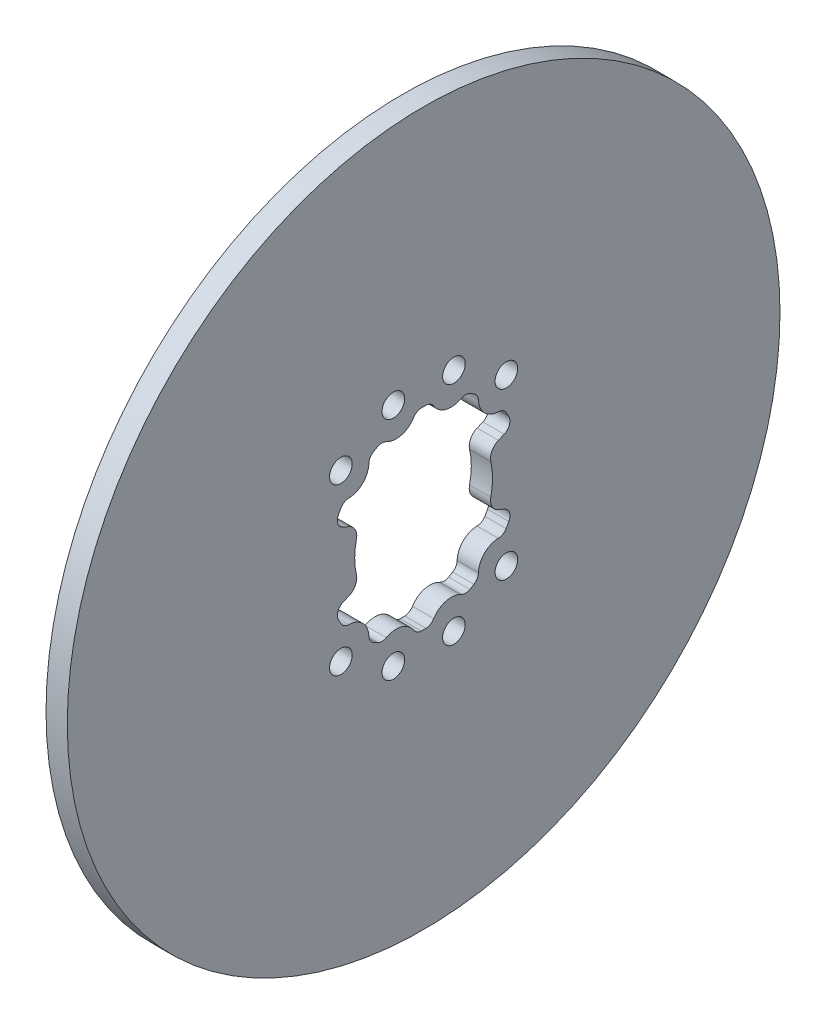
SolidWorks part; units mm, degrees
material "AR500"
ref_plane "Front Plane" through (0, 0, 0) normal (0, 0, 1) x (1, 0, 0)
ref_plane "Top Plane" through (0, 0, 0) normal (0, 1, 0) x (1, 0, 0)
ref_plane "Right Plane" through (0, 0, 0) normal (1, 0, 0) x (0, 0, -1)
sketch "Sketch1" plane through (0, 0, 0) normal (1, 0, 0) x (0, 0, -1)
  circle A0 centre (0, 0) radius 106.3625
  dimension "D1" = 212.725
extrude "Boss-Extrude1" add sketch "Sketch1" along normal blind 6.35
sketch "Sketch2" plane through (6.35, 0, 0) normal (1, 0, 0) x (0, 0, -1)
  line L0 (-9.0393, 33.735) -> (9.0393, 33.735) construction
  line B0 (22.31, -8.9662) -> (24.0357, -9.681)
  line B1 (-24.0357, -9.681) -> (-22.31, -8.9662)
  line B2 (-22.31, 8.9662) -> (-24.0357, 9.681)
  line B3 (24.0357, 9.681) -> (22.31, 8.9662)
  circle B4 centre (24.6957, -24.6957) radius 3.3782
  circle B5 centre (9.0393, -33.735) radius 3.3782
  circle B6 centre (-9.0393, -33.735) radius 3.3782
  circle B7 centre (-24.6957, -24.6957) radius 3.3782
  circle B8 centre (-24.6957, 24.6957) radius 3.3782
  circle B9 centre (-9.0393, 33.735) radius 3.3782
  circle B10 centre (9.0393, 33.735) radius 3.3782
  circle B11 centre (24.6957, 24.6957) radius 3.3782
  arc B12 (20.0543, -4.5952) -> (22.31, -8.9662) centre (23.768, -5.4462) ccw
  arc B13 (25.4311, -13.5782) -> (24.0357, -9.681) centre (22.9664, -12.2623) ccw
  arc B14 (24.6076, -15.0192) -> (25.4311, -13.5782) centre (0, 0) ccw
  arc B15 (22.2944, -16.3566) -> (24.6076, -15.0192) centre (22.2228, -13.5636) ccw
  arc B16 (22.2944, -16.3566) -> (16.3566, -22.2944) centre (22.4506, -22.4506) ccw
  arc B17 (15.0192, -24.6076) -> (16.3566, -22.2944) centre (13.5636, -22.2228) ccw
  arc B18 (13.8013, -25.3108) -> (15.0192, -24.6076) centre (0, 0) ccw
  arc B19 (11.1292, -25.3125) -> (13.8013, -25.3108) centre (12.4637, -22.8578) ccw
  arc B20 (11.1292, -25.3125) -> (3.0181, -27.4858) centre (8.2175, -30.6681) ccw
  arc B21 (0.7032, -28.8204) -> (3.0181, -27.4858) centre (0.635, -26.0273) ccw
  arc B22 (-0.7032, -28.8204) -> (0.7032, -28.8204) centre (0, 0) ccw
  arc B23 (-3.0181, -27.4858) -> (-0.7032, -28.8204) centre (-0.635, -26.0273) ccw
  arc B24 (-3.0181, -27.4858) -> (-11.1292, -25.3125) centre (-8.2175, -30.6681) ccw
  arc B25 (-13.8013, -25.3108) -> (-11.1292, -25.3125) centre (-12.4637, -22.8578) ccw
  arc B26 (-15.0192, -24.6076) -> (-13.8013, -25.3108) centre (0, 0) ccw
  arc B27 (-16.3566, -22.2944) -> (-15.0192, -24.6076) centre (-13.5636, -22.2228) ccw
  arc B28 (-16.3566, -22.2944) -> (-22.2944, -16.3566) centre (-22.4506, -22.4506) ccw
  arc B29 (-24.6076, -15.0192) -> (-22.2944, -16.3566) centre (-22.2228, -13.5636) ccw
  arc B30 (-25.4311, -13.5782) -> (-24.6076, -15.0192) centre (0, 0) ccw
  arc B31 (-24.0357, -9.681) -> (-25.4311, -13.5782) centre (-22.9664, -12.2623) ccw
  arc B32 (-22.31, -8.9662) -> (-20.0543, -4.5952) centre (-23.768, -5.4462) ccw
  arc B33 (-20.0543, 4.5952) -> (-20.0543, -4.5952) centre (0, 0) ccw
  arc B34 (-20.0543, 4.5952) -> (-22.31, 8.9662) centre (-23.768, 5.4462) ccw
  arc B35 (-25.4311, 13.5782) -> (-24.0357, 9.681) centre (-22.9664, 12.2623) ccw
  arc B36 (-24.6076, 15.0192) -> (-25.4311, 13.5782) centre (0, 0) ccw
  arc B37 (-22.2944, 16.3566) -> (-24.6076, 15.0192) centre (-22.2228, 13.5636) ccw
  arc B38 (-22.2944, 16.3566) -> (-16.3566, 22.2944) centre (-22.4506, 22.4506) ccw
  arc B39 (-15.0192, 24.6076) -> (-16.3566, 22.2944) centre (-13.5636, 22.2228) ccw
  arc B40 (-13.8013, 25.3108) -> (-15.0192, 24.6076) centre (0, 0) ccw
  arc B41 (-11.1292, 25.3125) -> (-13.8013, 25.3108) centre (-12.4637, 22.8578) ccw
  arc B42 (-11.1292, 25.3125) -> (-3.0181, 27.4858) centre (-8.2175, 30.6681) ccw
  arc B43 (-0.7032, 28.8204) -> (-3.0181, 27.4858) centre (-0.635, 26.0273) ccw
  arc B44 (0.7032, 28.8204) -> (-0.7032, 28.8204) centre (0, 0) ccw
  arc B45 (3.0181, 27.4858) -> (0.7032, 28.8204) centre (0.635, 26.0273) ccw
  arc B46 (3.0181, 27.4858) -> (11.1292, 25.3125) centre (8.2175, 30.6681) ccw
  arc B47 (13.8013, 25.3108) -> (11.1292, 25.3125) centre (12.4637, 22.8578) ccw
  arc B48 (15.0192, 24.6076) -> (13.8013, 25.3108) centre (0, 0) ccw
  arc B49 (16.3566, 22.2944) -> (15.0192, 24.6076) centre (13.5636, 22.2228) ccw
  arc B50 (16.3566, 22.2944) -> (22.2944, 16.3566) centre (22.4506, 22.4506) ccw
  arc B51 (24.6076, 15.0192) -> (22.2944, 16.3566) centre (22.2228, 13.5636) ccw
  arc B52 (25.4311, 13.5782) -> (24.6076, 15.0192) centre (0, 0) ccw
  arc B53 (24.0357, 9.681) -> (25.4311, 13.5782) centre (22.9664, 12.2623) ccw
  arc B54 (22.31, 8.9662) -> (20.0543, 4.5952) centre (23.768, 5.4462) ccw
  arc B55 (20.0543, -4.5952) -> (20.0543, 4.5952) centre (0, 0) ccw
sketch_block_instance "WeaponMounting-1"
sketch_block "WeaponMounting"
extrude "Cut-Extrude1" cut sketch "Sketch2" against normal through all
